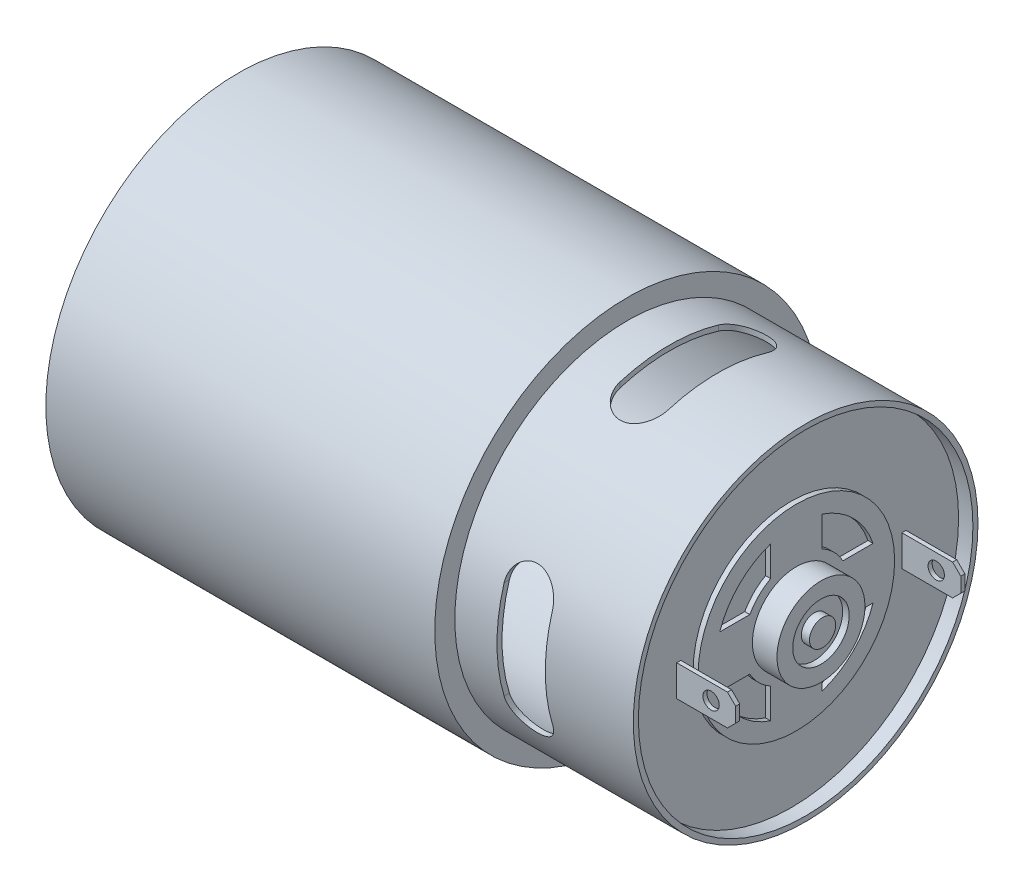
SolidWorks part; units mm, degrees
material "Chrome Stainless Steel"
ref_plane "Front Plane" through (0, 0, 0) normal (0, 0, 1) x (1, 0, 0)
ref_plane "Top Plane" through (0, 0, 0) normal (0, 1, 0) x (1, 0, 0)
ref_plane "Right Plane" through (0, 0, 0) normal (1, 0, 0) x (0, 0, -1)
sketch "Sketch1" plane through (0, 0, 0) normal (0, 0, 1) x (1, 0, 0)
  line L0 (-77.87, 6.5) -> (-77.87, 2.5)
  line L1 (-77.87, 2.5) -> (-82.97, 2.5)
  line L2 (-4.44, 0) -> (0, 0)
  line L3 (-85.47, 0) -> (-72.75, 0)
  line L9 (0, 0) -> (-92.3389, 0) construction
  line L12 (-72.75, 0) -> (-72.75, 19.05)
  line L13 (-71.37, 20.43) -> (-4.44, 20.43)
  line L15 (-2.07, 21.05) -> (-23.87, 21.05)
  line L16 (-23.87, 21.05) -> (-23.87, 23.5)
  line L17 (-23.87, 23.5) -> (-71.37, 23.5)
  line L18 (-71.37, 23.5) -> (-71.37, 21.05)
  line L19 (-73.37, 19.05) -> (-73.37, 6.5)
  line L20 (-73.37, 6.5) -> (-77.87, 6.5)
  line L21 (-1, 3.45) -> (-0.2, 3.45)
  line L22 (-0.2, 3.45) -> (-0.2, 5.375)
  line L23 (-0.2, 5.375) -> (-3.2, 5.375)
  line L24 (-3.2, 5.375) -> (-3.2, 12)
  line L25 (-3.2, 12) -> (-3.82, 12)
  line L26 (-3.82, 12) -> (-3.82, 20.43)
  line L27 (-3.82, 20.43) -> (-2.07, 20.43)
  line L28 (-2.07, 20.43) -> (-2.07, 21.05)
  line L32 (-4.44, 20.43) -> (-4.44, 0)
  line L46 (0, 0) -> (0, 1.6)
  line L47 (0, 1.6) -> (-1, 1.6)
  line L48 (-1, 1.6) -> (-1, 3.45)
  arc A0 (-82.97, 2.5) -> (-85.47, 0) centre (-82.97, 0) ccw
  arc A5 (-71.37, 20.43) -> (-72.75, 19.05) centre (-71.37, 19.05) ccw
  arc A6 (-71.37, 21.05) -> (-73.37, 19.05) centre (-71.37, 19.05) ccw
  dimension "D1" = 2.5
  dimension "D2" = 1.38
  dimension "D3" = 2
  dimension "D4" = 13
  dimension "D5" = 0.2
  dimension "D6" = 1
  dimension "D7" = 2.07
  dimension "D8" = 3.2
  dimension "D9" = 72.75
  dimension "D10" = 4.44
  dimension "D11" = 23.87
  dimension "D12" = 1.6
  dimension "D13" = 3.45
  dimension "D14" = 77.87
  dimension "D15" = 85.47
  dimension "D16" = 5.375
  dimension "D17" = 12
  dimension "D18" = 20.43
  dimension "D20" = 23.5
revolve "Revolve1" add sketch "Sketch1" angle 360 mid plane about L9
sketch "Sketch2" plane through (0, 0, 0) normal (0, 0, 1) x (1, 0, 0)
  line L0 (-18.72, 6) -> (-18.72, -6)
  line L1 (-12.82, -6) -> (-12.82, 6)
  line L2 (0, 0) -> (-49.2336, 0) construction
  line L3 (-2.07, -21.05) -> (-2.07, 21.05) construction
  arc A0 (-12.82, 6) -> (-18.72, 6) centre (-15.77, 6) ccw
  arc A1 (-18.72, -6) -> (-12.82, -6) centre (-15.77, -6) ccw
  dimension "D1" = 5.9
  dimension "D2" = 12
  dimension "D3" = 10.75
extrude "Extrude1" cut sketch "Sketch2" against normal through all and the other way through all
pattern_circular "CirPattern1" count 4 over 360 about axis through (0, 0, 0) along (1, 0, 0) of "Extrude1"
sketch "Sketch3" plane through (-73.37, 0, 0) normal (-1, 0, 0) x (0, 0, 1)
  line L0 (15.4548, 4.1411) -> (11.5911, 3.1058)
  line L1 (3.1058, 11.5911) -> (4.1411, 15.4548)
  line L2 (0, 0) -> (11.3137, 11.3137) construction
  line L3 (0, 0) -> (12.9303, 0) construction
  arc A0 (15.4548, 4.1411) -> (4.1411, 15.4548) centre (0, 0) ccw
  arc A1 (11.5911, 3.1058) -> (3.1058, 11.5911) centre (0, 0) ccw
  dimension "D1" = 16
  dimension "D2" = 12
  dimension "D3" = 60
  dimension "D4" = 4
  dimension "D5" = 45
extrude "Extrude2" cut sketch "Sketch3" against normal up to next
pattern_circular "CirPattern2" count 4 over 360 about axis through (0, 0, 0) along (1, 0, 0) of "Extrude2"
sketch "Sketch4" plane through (-73.37, 0, 0) normal (-1, 0, 0) x (0, 0, 1)
  line L0 (0, 0) -> (17.1315, 0) construction
  line L1 (0, 0) -> (0, 9.404) construction
  circle A0 centre (12.5, 0) radius 1.25
  circle A1 centre (-12.5, 0) radius 1.25
  dimension "D1" = 2.5
  dimension "D2" = 12.5
extrude "Extrude3" cut sketch "Sketch4" against normal up to next
sketch "Sketch5" plane through (-3.2, 0, 0) normal (1, 0, 0) x (0, 0, -1)
  line L0 (9.3591, 3.15) -> (5.6857, 3.15)
  line L1 (3.15, 5.6857) -> (3.15, 9.3591)
  arc A0 (9.3591, 3.15) -> (3.15, 9.3591) centre (0, 0) ccw
  arc A1 (5.6857, 3.15) -> (3.15, 5.6857) centre (0, 0) ccw
  dimension "D1" = 9.875
  dimension "D2" = 6.5
  dimension "D3" = 6.2091
  dimension "D4" = 3.6734
extrude "Extrude4" cut sketch "Sketch5" against normal up to surface (0.62 mm away) up to face at (-3.82, 0, -20.43)
pattern_circular "CirPattern3" count 4 over 360 about axis through (0, 0, 0) along (1, 0, 0) of "Extrude4"
ref_plane "Plane1" through (0, 0, 14) normal (0, 0, 1) x (1, 0, 0)
sketch "Sketch6" plane through (0, 0, 14) normal (0, 0, 1) x (1, 0, 0)
  line L0 (0, 0) -> (7.2152, 0) construction
  line L1 (-3.82, -1.9) -> (3.38, -1.9)
  line L2 (-3.82, -1.9) -> (-3.82, 1.9)
  line L3 (-3.82, 1.9) -> (3.38, 1.9)
  line L4 (3.38, -1.9) -> (3.38, 1.9)
  line L5 (-3.82, -12) -> (-3.82, 12) construction
  dimension "D1" = 7.2
  dimension "D2" = 3.8
extrude "Extrude7" add sketch "Sketch6" against normal blind 0.5
sketch "Sketch7" plane through (0, 0, 14) normal (0, 0, 1) x (1, 0, 0)
  line L0 (3.38, -1.9) -> (3.38, 1.9) construction
  line L1 (3.38, 0) -> (-1.2681, 0) construction
  circle A0 centre (0.38, 0) radius 1
  dimension "D1" = 2
  dimension "D2" = 3
extrude "Extrude9" cut sketch "Sketch7" against normal up to next
chamfer "Chamfer1" distance 1 angle 45 2 edges at (3.38, -1.9, 13.75) (3.38, 1.9, 13.75)
mirror "Mirror1" about plane through (0, 0, 0) normal (0, 0, 1) of "Chamfer1", "Extrude9", "Extrude7"
fillet "Fillet1" radius 0.5 2 edges at (-77.87, 0, -6.5) (-73.37, 0, -6.5)
